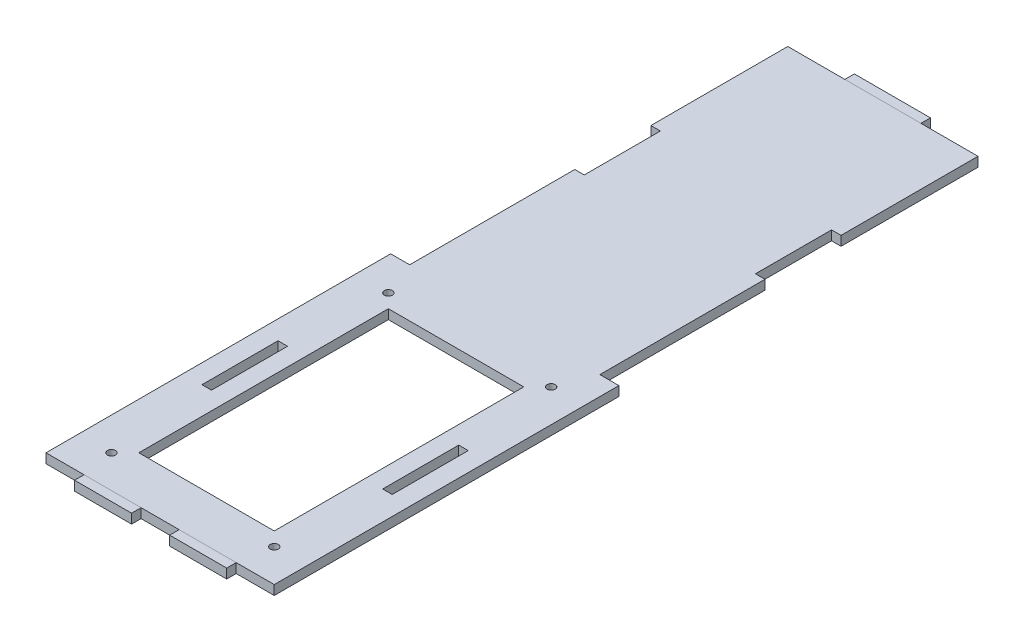
SolidWorks part; units mm, degrees
ref_plane "Front Plane" through (0, 0, 0) normal (0, 0, 1) x (1, 0, 0)
ref_plane "Top Plane" through (0, 0, 0) normal (0, 1, 0) x (1, 0, 0)
ref_plane "Right Plane" through (0, 0, 0) normal (1, 0, 0) x (0, 0, -1)
sketch "Sketch1" plane through (0, 0, 0) normal (0, 1, 0) x (1, 0, 0)
  line L0 (0, 0) -> (38.1, 0) construction
  line L1 (38.1, 0) -> (38.1, 120.65) construction
  line L2 (0, -120.65) -> (0, -114.3) construction
  line L3 (38.1, 120.65) -> (-38.1, 120.65)
  line L4 (38.1, 120.65) -> (38.1, -120.65)
  line L5 (38.1, -120.65) -> (-38.1, -120.65)
  line L6 (-38.1, 120.65) -> (-38.1, -120.65)
  line L7 (-31.75, -114.3) -> (31.75, -114.3)
  line L8 (-31.75, -109.728) -> (-27.178, -109.728) construction
  line L9 (31.75, -114.3) -> (31.75, -109.728) construction
  line L10 (-31.75, -12.7) -> (31.75, -12.7) construction
  line L11 (-31.75, -114.3) -> (-31.75, -109.728) construction
  line L12 (31.75, -109.728) -> (27.178, -109.728) construction
  line L13 (-31.75, -12.7) -> (-31.75, -17.272) construction
  line L14 (-31.75, -17.272) -> (-27.178, -17.272) construction
  line L15 (31.75, -12.7) -> (31.75, -17.272) construction
  line L16 (31.75, -17.272) -> (27.178, -17.272) construction
  line L17 (31.75, -17.272) -> (31.75, -21.844) construction
  line L18 (31.75, -21.844) -> (22.606, -21.844) construction
  line L20 (22.606, -21.844) -> (-22.606, -21.844)
  line L21 (22.606, -21.844) -> (22.606, -105.156)
  line L22 (22.606, -105.156) -> (-22.606, -105.156)
  line L23 (-22.606, -21.844) -> (-22.606, -105.156)
  circle A0 centre (-27.178, -109.728) radius 1.35
  circle A1 centre (27.178, -109.728) radius 1.35
  circle A2 centre (-27.178, -17.272) radius 1.35
  circle A3 centre (27.178, -17.272) radius 1.35
  point P12 (0, -114.3)
  dimension "D10" = 2.7
  dimension "D13" = 2.7
  dimension "D16" = 2.7
  dimension "D17" = 2.7
  dimension "D1" = 38.1
  dimension "D2" = 120.65
  dimension "D3" = 76.2
  dimension "D4" = 241.3
  dimension "D5" = 6.35
  dimension "D6" = 101.6
  dimension "D7" = 101.6
  dimension "D8" = 4.572
  dimension "D9" = 4.572
  dimension "D11" = 4.572
  dimension "D12" = 4.572
  dimension "D14" = 4.572
  dimension "D15" = 4.572
  dimension "D18" = 4.572
  dimension "D19" = 9.144
  dimension "D20" = 83.312
  dimension "D21" = 45.212
extrude "Boss-Extrude1" add sketch "Sketch1" along normal blind 3.175 contours L4 L5 L6 L3
extrude "Cut-Extrude2" cut sketch "Sketch1<3>" along normal blind 3.175 contours L20 L23 L22 L21
sketch "Sketch1<3>" plane through (0, 0, 0) normal (0, 1, 0) x (1, 0, 0) same geometry as "Sketch1"
extrude "Cut-Extrude5" cut sketch "Sketch1<5>" along normal blind 3.175 contours A2
sketch "Sketch1<5>" plane through (0, 0, 0) normal (0, 1, 0) x (1, 0, 0) same geometry as "Sketch1"
extrude "Cut-Extrude6" cut sketch "Sketch1<6>" along normal blind 3.175 contours A3
sketch "Sketch1<6>" plane through (0, 0, 0) normal (0, 1, 0) x (1, 0, 0) same geometry as "Sketch1"
extrude "Cut-Extrude7" cut sketch "Sketch1<7>" along normal blind 3.175 contours A0
sketch "Sketch1<7>" plane through (0, 0, 0) normal (0, 1, 0) x (1, 0, 0) same geometry as "Sketch1"
extrude "Cut-Extrude9" cut sketch "Sketch1<8>" along normal blind 3.175 contours A1
sketch "Sketch1<8>" plane through (0, 0, 0) normal (0, 1, 0) x (1, 0, 0) same geometry as "Sketch1"
sketch "Sketch5" plane through (0, 3.175, 0) normal (0, 1, 0) x (1, 0, 0)
  line L0 (0, -120.65) -> (0, -5.588) construction
  line L1 (38.1, -120.65) -> (-38.1, -120.65) construction
  line L2 (0, -5.588) -> (-31.75, -5.588) construction
  line L3 (0, -5.588) -> (31.75, -5.588) construction
  line L4 (-31.75, -5.588) -> (-38.1, -5.588)
  line L5 (-38.1, 120.65) -> (-38.1, -120.65) construction
  line L6 (-38.1, -5.588) -> (-31.75, -5.588)
  line L7 (-31.75, -5.588) -> (-31.75, 120.65)
  line L8 (38.1, 120.65) -> (-38.1, 120.65) construction
  line L9 (-31.75, 120.65) -> (-38.1, 120.65)
  line L10 (-38.1, 120.65) -> (-38.1, -5.588)
  line L11 (31.75, -5.588) -> (31.75, 120.65)
  line L12 (31.75, 120.65) -> (38.1, 120.65)
  line L13 (38.1, 120.65) -> (38.1, -5.588)
  line L14 (38.1, 120.65) -> (38.1, -120.65) construction
  line L15 (38.1, -5.588) -> (31.75, -5.588)
  line M10 (38.1, 120.65) -> (-38.1, 120.65)
  line M11 (-38.1, 120.65) -> (-38.1, -120.65)
  line M13 (38.1, -120.65) -> (38.1, 120.65)
  dimension "D1" = 115.062
extrude "Cut-Extrude11" cut sketch "Sketch5" against normal blind 3.175 contours L4 L7 M10 M11 region at (-34.925, 3.175, -57.531)
extrude "Cut-Extrude12" cut sketch "Sketch5<4>" against normal blind 3.175 contours L15 L11 M13 M10 region at (34.925, 3.175, -57.531)
sketch "Sketch5<4>" plane through (0, 3.175, 0) normal (0, 1, 0) x (1, 0, 0) same geometry as "Sketch5"
sketch "Sketch7" plane through (0, 3.175, 0) normal (0, 1, 0) x (1, 0, 0)
  line L0 (-38.1, -120.65) -> (-31.75, -120.65) construction
  line L1 (38.1, -120.65) -> (-38.1, -120.65) construction
  line L2 (-31.75, -120.65) -> (-31.75, -74.93) construction
  line L3 (-31.75, -74.93) -> (-28.575, -74.93) construction
  line L4 (-28.575, -74.93) -> (-28.575, -49.53)
  line L5 (-31.75, -74.93) -> (-31.75, -49.53)
  line L6 (-31.75, -49.53) -> (-28.575, -49.53)
  line L7 (-28.575, -74.93) -> (-31.75, -74.93)
  line L8 (38.1, -120.65) -> (31.75, -120.65) construction
  line L9 (31.75, -120.65) -> (31.75, -74.93) construction
  line L10 (31.75, -74.93) -> (28.575, -74.93)
  line L11 (28.575, -74.93) -> (28.575, -49.53)
  line L12 (28.575, -49.53) -> (31.75, -49.53)
  line L13 (31.75, -49.53) -> (31.75, -74.93)
  line L14 (-31.75, 120.65) -> (-31.75, 74.93) construction
  line L15 (-31.75, -5.588) -> (-31.75, 120.65) construction
  line L16 (-31.75, 74.93) -> (-28.575, 74.93)
  line L17 (-28.575, 74.93) -> (-28.575, 49.53)
  line L18 (-28.575, 49.53) -> (-31.75, 49.53)
  line L19 (-31.75, 49.53) -> (-31.75, 74.93)
  line L20 (31.75, 120.65) -> (31.75, 74.93) construction
  line L21 (31.75, -5.588) -> (31.75, 120.65) construction
  line L22 (31.75, 74.93) -> (28.575, 74.93)
  line L23 (28.575, 74.93) -> (28.575, 49.53)
  line L24 (28.575, 49.53) -> (31.75, 49.53)
  line L25 (31.75, 49.53) -> (31.75, 74.93)
  dimension "D1" = 25.4
extrude "Cut-Extrude13" cut sketch "Sketch7" against normal blind 3.175 contours L7 L5 L6 L4
extrude "Cut-Extrude14" cut sketch "Sketch7<3>" against normal blind 3.175
sketch "Sketch7<3>" plane through (0, 3.175, 0) normal (0, 1, 0) x (1, 0, 0) same geometry as "Sketch7"
sketch "Sketch8" plane through (0, 3.175, 0) normal (0, 1, 0) x (1, 0, 0)
  line L0 (-38.1, -120.65) -> (-25.4, -120.65) construction
  line L1 (38.1, -120.65) -> (-38.1, -120.65) construction
  line L2 (-25.4, -120.65) -> (-25.4, -123.825)
  line L3 (-25.4, -123.825) -> (-6.35, -123.825)
  line L4 (-6.35, -123.825) -> (-6.35, -120.65)
  line L5 (-6.35, -120.65) -> (-25.4, -120.65)
  line L6 (-6.35, -120.65) -> (6.35, -120.65) construction
  line L11 (6.35, -120.65) -> (6.35, -123.825)
  line L12 (6.35, -123.825) -> (25.4, -123.825)
  line L13 (25.4, -123.825) -> (25.4, -120.65)
  line L14 (25.4, -120.65) -> (6.35, -120.65)
  line L15 (0, 120.65) -> (-12.7, 120.65) construction
  line L16 (31.75, 120.65) -> (-31.75, 120.65) construction
  line L17 (-12.7, 120.65) -> (-12.7, 123.825)
  line L18 (-12.7, 123.825) -> (12.7, 123.825)
  line L19 (12.7, 123.825) -> (12.7, 120.65)
  line L20 (12.7, 120.65) -> (-12.7, 120.65)
  dimension "D1" = 12.7
  dimension "D2" = 19.05
extrude "Boss-Extrude2" add sketch "Sketch8" against normal blind 3.175 separate body
